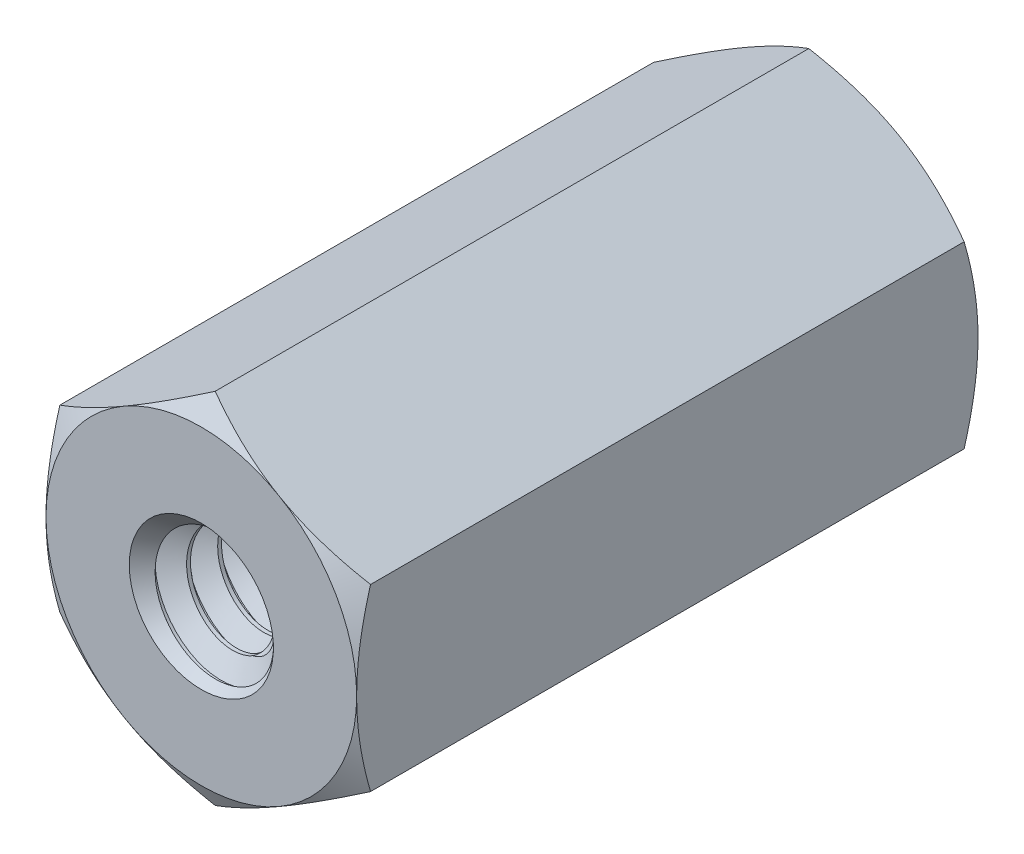
SolidWorks part; units mm, degrees
ref_plane "Front Plane" through (0, 0, 0) normal (0, 0, 1) x (1, 0, 0)
ref_plane "Top Plane" through (0, 0, 0) normal (0, 1, 0) x (1, 0, 0)
ref_plane "Right Plane" through (0, 0, 0) normal (1, 0, 0) x (0, 0, -1)
sketch "Sketch3" plane through (0, 0, 0) normal (1, 0, 0) x (0, 0, -1)
  line L0 (-6.35, 0) -> (6.35, 0) construction
  line L1 (0, 3.175) -> (0, -3.175) construction
  line L2 (-6.35, 1.4224) -> (-6.35, -1.4224) construction
  point P2 (1.5875, 0)
  point P3 (-1.5875, 0)
  dimension "D1" = 4.7625
  dimension "Length" = 12.7
  dimension "Min Thread Length" = 4.7625
  dimension "Thread Dia" = 2.8448
  dimension "Hex" = 6.35
sketch "Sketch1" plane through (0, 0, 0) normal (0, 0, 1) x (1, 0, 0)
  line L1 (0, 3.6662) -> (-3.175, 1.8331)
  line L2 (-3.175, 1.8331) -> (-3.175, -1.8331)
  line L3 (-3.175, -1.8331) -> (0, -3.6662)
  line L4 (0, -3.6662) -> (3.175, -1.8331)
  line L5 (3.175, -1.8331) -> (3.175, 1.8331)
  line L6 (3.175, 1.8331) -> (0, 3.6662)
  circle A0 centre (0, 0) radius 3.175 construction
  circle A1 centre (0, 0) radius 1.4224
extrude "Extrude1" add sketch "Sketch1" along normal up to vertex (6.35 mm away) and the other way up to vertex (6.35 mm away) up to point (0, 0, 6.35) other way up to point (0, 0, -6.35)
sketch "Sketch11" plane through (0, 0, -6.35) normal (0, 0, -1) x (-1, 0, 0)
  circle A0 centre (0, 0) radius 1.4224 construction
  circle A1 centre (0, 0) radius 1.4224
curve "Helix/Spiral1" pitch 0.635 height 13.335 radius 1.4224 centre (0, 0, -6.35) axis (0, 0, 1) start towards (0, 1, 0) parameters "Pitch"=0.635
sketch "Sketch12" plane through (0, 0, 0) normal (1, 0, 0) x (0, 0, -1)
  line L0 (6.9056, 1.4224) -> (6.35, 1.4224)
  line L1 (6.9056, 1.4224) -> (6.6675, 1.01)
  line L2 (6.6675, 1.01) -> (6.5881, 1.01)
  line L3 (6.5881, 1.01) -> (6.35, 1.4224)
  line L4 (6.6278, 1.01) -> (6.6278, 1.4224) construction
  line L5 (6.7866, 1.2162) -> (6.4691, 1.2162) construction
  dimension "D1" = 0.0794
  dimension "D2" = 0.3175
  dimension "D3" = 60
sweep "Sweep1" add profiles "Sketch12" path "Helix/Spiral1"
sketch "Sketch6" plane through (0, 0, -6.35) normal (0, 0, -1) x (-1, 0, 0)
  line L6 (0, 3.6662) -> (-3.175, 1.8331)
  line L7 (-3.175, 1.8331) -> (-3.175, -1.8331)
  line L8 (-3.175, -1.8331) -> (0, -3.6662)
  line L9 (0, -3.6662) -> (3.175, -1.8331)
  line L10 (3.175, -1.8331) -> (3.175, 1.8331)
  line L11 (3.175, 1.8331) -> (0, 3.6662)
  line L12 (0, 3.6662) -> (-3.175, 1.8331)
  line L13 (-3.175, 1.8331) -> (-3.175, -1.8331)
  line L14 (-3.175, -1.8331) -> (0, -3.6662)
  line L15 (0, -3.6662) -> (3.175, -1.8331)
  line L16 (3.175, -1.8331) -> (3.175, 1.8331)
  line L17 (3.175, 1.8331) -> (0, 3.6662)
  dimension "D1" = 0
extrude "Extrude2" cut sketch "Sketch6" along normal through all
sketch "Sketch7" plane through (0, 0, -6.35) normal (0, 0, -1) x (-1, 0, 0)
  circle A2 centre (0, 0) radius 1.4732
  circle A3 centre (0, 0) radius 1.4732
  dimension "D1" = 0.0508
extrude "Extrude3" cut sketch "Sketch7" against normal through all draft 43
sketch "Sketch8" plane through (0, 0, -6.35) normal (0, 0, -1) x (-1, 0, 0)
  circle A0 centre (0, 0) radius 3.175 construction
  circle A1 centre (0, 0) radius 3.175
extrude "Extrude4" cut sketch "Sketch8" against normal through all draft 60 flip side to cut
mirror "Mirror1" about plane through (0, 0, 0) normal (0, 0, 1) of "Extrude2", "Extrude3", "Extrude4"
sketch "Sketch9" [suppressed] plane through (0, 0, 0) normal (1, 0, 0) x (0, 0, -1)
  line L1 (-1.5875, 0.8128) -> (1.5875, 0.8128)
  line L2 (-1.5875, 0.8128) -> (-1.5875, 0)
  line L3 (-1.5875, 0) -> (1.5875, 0)
  line L4 (1.5875, 0.8128) -> (1.5875, 0)
  line L7 (-6.35, 0) -> (6.35, 0) construction
revolve "Revolve" [suppressed] add sketch "Sketch9" angle 360 about L0
sketch "Sketch10" [suppressed] plane through (0, 0, 0) normal (1, 0, 0) x (0, 0, -1)
  line L0 (6.35, 0.762) -> (1.5875, 0.762)
  line L1 (-6.35, 0.762) -> (-1.5875, 0.762)
  line L2 (1.5875, 0.762) -> (1.5875, -0.762)
  line L3 (-6.35, -0.8128) -> (-1.5875, -0.8128)
  line L4 (-1.5875, 0.762) -> (-1.5875, -0.8128)
  line L5 (1.5875, -0.762) -> (6.35, -0.762)
equation "\"D1@Sketch3\" = \"Min Thread Length@Sketch3\""
equation "\"D3@Helix/Spiral1\" = \"Length@Sketch3\"+\"Pitch@Helix/Spiral1\""
equation "\"D1@Sketch12\" = \"Pitch@Helix/Spiral1\"*.125"
equation "\"D2@Sketch12\" = \"Pitch@Helix/Spiral1\"*.5"
